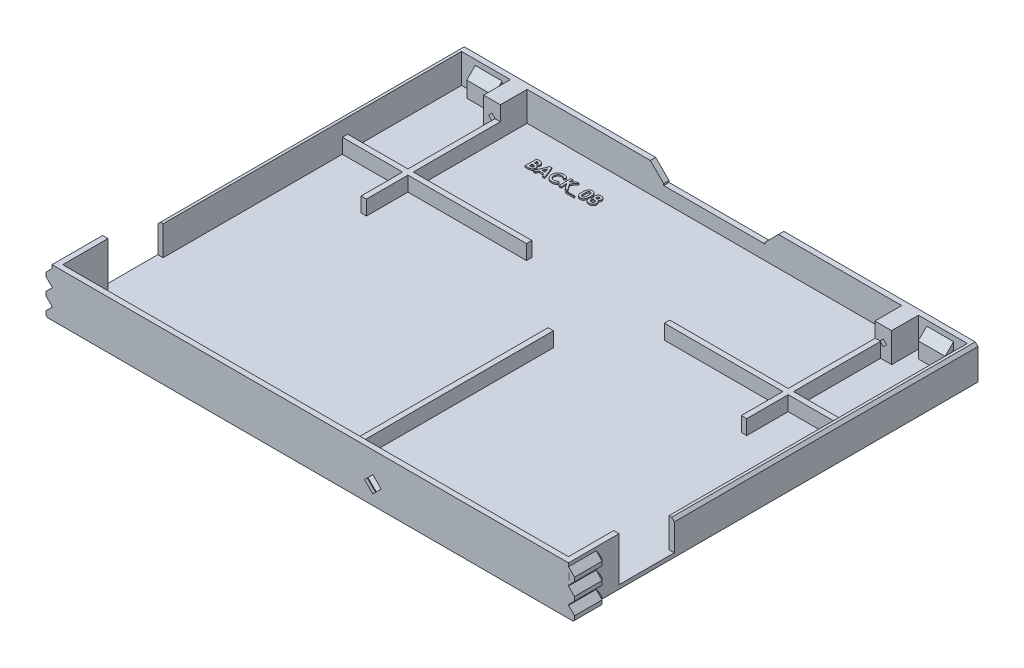
SolidWorks part; units mm, degrees
ref_plane "Front Plane" through (0, 0, 0) normal (0, 0, 1) x (1, 0, 0)
ref_plane "Top Plane" through (0, 0, 0) normal (0, 1, 0) x (1, 0, 0)
ref_plane "Right Plane" through (0, 0, 0) normal (1, 0, 0) x (0, 0, -1)
sketch "Sketch1" plane through (0, 0, 0) normal (0, 1, 0) x (1, 0, 0)
  line L3 (-77.15, -61.17) -> (77.15, -61.17)
  line L5 (-77.15, 61.17) -> (77.15, -61.17) construction
  line L6 (-77.15, -61.17) -> (77.15, 61.17) construction
  line L13 (-77.15, 61.17) -> (-77.15, -61.17)
  line L18 (77.15, 61.17) -> (-77.15, 61.17)
  line L20 (77.15, 61.17) -> (77.15, -61.17)
  point P0 (0, 0)
  point P6 (0, 0)
  dimension "D3" = 154.3
  dimension "D1" = 154.3
  dimension "D2" = 122.34
extrude "flat_on_wall" add sketch "Sketch1" along normal blind 1.2
sketch "Sketch3" plane through (0, 0, 0) normal (0, 1, 0) x (1, 0, 0)
  line L0 (-77.15, -29.57) -> (-77.15, 61.17)
  line L1 (-77.15, 61.17) -> (-77.15, -61.17) construction
  line L2 (-77.15, 61.17) -> (-45.55, 61.17)
  line L3 (77.15, 61.17) -> (-77.15, 61.17) construction
  line L6 (-75.55, 59.57) -> (-75.55, -29.57)
  line L7 (-75.55, -29.57) -> (-77.15, -29.57)
  line L8 (45.55, 61.17) -> (77.15, 61.17)
  line L9 (77.15, 61.17) -> (77.15, -29.57)
  line L10 (77.15, -61.17) -> (77.15, 61.17) construction
  line L11 (77.15, -29.57) -> (75.55, -29.57)
  line L12 (75.55, -29.57) -> (75.55, 59.57)
  line L15 (-77.15, -46.07) -> (-77.15, -61.17)
  line L16 (-77.15, -61.17) -> (77.15, -61.17)
  line L17 (77.15, -61.17) -> (77.15, -46.07)
  line L18 (77.15, -46.07) -> (75.55, -46.07)
  line L19 (75.55, -46.07) -> (75.55, -59.57)
  line L20 (75.55, -59.57) -> (-75.55, -59.57)
  line L21 (-75.55, -59.57) -> (-75.55, -46.07)
  line L22 (-75.55, -46.07) -> (-77.15, -46.07)
  line L23 (-75.55, 59.57) -> (-60.95, 59.57)
  line L24 (-60.95, 59.57) -> (-60.95, 51.57)
  line L25 (-60.95, 51.57) -> (-55.95, 51.57)
  line L26 (-55.95, 51.57) -> (-55.95, 59.57)
  line L27 (-55.95, 59.57) -> (-45.55, 59.57)
  line L28 (75.55, 59.57) -> (60.95, 59.57)
  line L29 (60.95, 59.57) -> (60.95, 51.57)
  line L30 (60.95, 51.57) -> (55.95, 51.57)
  line L31 (55.95, 51.57) -> (55.95, 59.57)
  line L32 (55.95, 59.57) -> (45.55, 59.57)
  line L34 (-45.55, 59.57) -> (45.55, 59.57)
  line L36 (-45.55, 61.17) -> (45.55, 61.17)
  point P25 (-76.35, -46.07)
  dimension "D2" = 1.6
  dimension "D3" = 30
  dimension "D4" = 16.5
  dimension "D5" = 5
  dimension "D6" = 1.6
  dimension "D7" = 30
  dimension "D8" = 16.5
  dimension "D9" = 1.6
  dimension "D10" = 13.5
  dimension "D11" = 1.6
  dimension "D12" = 1.6
  dimension "D13" = 13.5
  dimension "D14" = 14.6
  dimension "D15" = 5
  dimension "D16" = 8
  dimension "D17" = 8
  dimension "D18" = 8
  dimension "D19" = 8
  dimension "D20" = 1.6
  dimension "D21" = 14.6
  dimension "D22" = 1.6
  dimension "D23" = 1.6
extrude "walls" add sketch "Sketch3" along normal blind 10
sketch "Sketch5" plane through (0, 0, 0) normal (1, 0, 0) x (0, 0, -1)
  line L0 (-61.17, 10) -> (-61.17, 0) construction
  line L5 (-61.17, 0) -> (-51.97, 0)
  line L6 (-61.17, 0) -> (-61.17, 2)
  line L7 (-61.17, 2) -> (-51.97, 2)
  line L8 (-51.97, 0) -> (-51.97, 2)
  line L9 (-61.17, 0) -> (61.17, 0) construction
  line L10 (-61.17, 10) -> (-51.97, 10)
  line L11 (-61.17, 5) -> (-51.97, 5)
  line L12 (-61.17, 5) -> (-61.17, 7)
  line L13 (-61.17, 7) -> (-51.97, 7)
  line L14 (-51.97, 5) -> (-51.97, 7)
  line L15 (-61.17, 10) -> (-61.17, 12)
  line L16 (-61.17, 12) -> (-51.97, 12)
  line L17 (-51.97, 10) -> (-51.97, 12)
  line L18 (-61.17, 10) -> (-46.07, 10) construction
  dimension "D1" = 0
  dimension "D2" = 9.2
  dimension "D3" = 2
  dimension "D4" = 9.2
  dimension "D5" = 2
  dimension "D6" = 3
  dimension "D7" = 2
extrude "rails" add sketch "Sketch5" along normal blind 0.75 from surface starting at face at (77.15, 5.3, 18.91)
sketch "Sketch6" plane through (0, 0, 0) normal (1, 0, 0) x (0, 0, -1)
  line L0 (-61.17, 12) -> (-51.97, 12)
  line L1 (-61.17, 2) -> (-51.97, 2)
  line L2 (-61.17, 2) -> (-61.17, 0)
  line L3 (-61.17, 0) -> (-51.97, 0)
  line L4 (-51.97, 2) -> (-51.97, 0)
  line L5 (-61.17, 7) -> (-51.97, 7)
  line L6 (-61.17, 7) -> (-61.17, 5)
  line L7 (-61.17, 5) -> (-51.97, 5)
  line L8 (-51.97, 7) -> (-51.97, 5)
  line L9 (-61.17, 12) -> (-61.17, 10)
  line L10 (-61.17, 10) -> (-51.97, 10)
  line L11 (-51.97, 12) -> (-51.97, 10)
  dimension "D1" = 9.2
  dimension "D2" = 9.2
  dimension "D3" = 2
  dimension "D4" = 2
  dimension "D5" = 2
extrude "rails-left" add sketch "Sketch6" along normal blind 0.1 and the other way blind 1.8 from surface starting at face at (-77.15, 5.3, 18.91)
sketch "Sketch7" plane through (0, 0, 0) normal (0, 1, 0) x (1, 0, 0)
  line L0 (-47.15, 46.17) -> (-47.15, 39.9043) construction
  line L1 (-44.69, 46.17) -> (-44.69, 43.37)
  line L2 (-49.61, 46.17) -> (-49.61, 43.37)
  line L3 (77.15, 61.17) -> (-77.15, 61.17) construction
  line L4 (-77.15, -29.57) -> (-77.15, -46.07) construction
  line L5 (47.15, 46.17) -> (47.15, 39.9043) construction
  line L6 (49.61, 46.17) -> (49.61, 43.37)
  line L7 (44.69, 46.17) -> (44.69, 43.37)
  line L9 (77.15, -29.57) -> (77.15, 61.17) construction
  line L10 (77.15, 61.17) -> (-77.15, 61.17) construction
  line L13 (-77.05, -61.17) -> (77.15, -61.17) construction
  line L14 (-0.45, 8.83) -> (-0.45, 2.5643) construction
  line L15 (2.01, 8.83) -> (2.01, 6.03)
  line L16 (-2.91, 8.83) -> (-2.91, 6.03)
  line L17 (77.15, -46.07) -> (77.15, -29.57) construction
  arc A0 (-44.69, 46.17) -> (-49.61, 46.17) centre (-47.15, 46.17) ccw
  arc A3 (-44.69, 43.37) -> (-49.61, 43.37) centre (-47.15, 39.9043) cw
  arc A4 (49.61, 46.17) -> (44.69, 46.17) centre (47.15, 46.17) ccw
  arc A5 (49.61, 43.37) -> (44.69, 43.37) centre (47.15, 39.9043) cw
  arc A8 (2.01, 8.83) -> (-2.91, 8.83) centre (-0.45, 8.83) ccw
  arc A9 (2.01, 6.03) -> (-2.91, 6.03) centre (-0.45, 2.5643) cw
  point P2 (-47.9176, 44.8712)
  point P13 (43.1175, 41.9506)
  dimension "D1" = 15
  dimension "D5" = 2.46
  dimension "D9" = 4.25
  dimension "D2" = 30
  dimension "D3" = 15
  dimension "D4" = 30
  dimension "D6" = 6.2657
  dimension "D7" = 77.6
  dimension "D8" = 70
extrude "Cut-Extrude7" [suppressed] cut sketch "Sketch7" against normal through all from surface starting at face at (0, 1.2, -7.1)
sketch "Sketch8" plane through (0, 0, -51.57) normal (0, 0, 1) x (1, 0, 0)
  line L0 (-60.95, 10) -> (-60.95, 1.2) construction
  line L1 (-60.95, 10) -> (-55.95, 10) construction
  line L2 (55.95, 10) -> (55.95, 1.2) construction
  line L3 (55.95, 10) -> (60.95, 10) construction
  line L4 (-75.55, 10) -> (-60.95, 10) construction
  line L5 (-63.45, 3) -> (-71.45, 3)
  line L6 (-63.45, 3) -> (-63.45, 8)
  line L7 (-63.45, 8) -> (-71.45, 8)
  line L8 (-71.45, 3) -> (-71.45, 8)
  line L9 (-60.95, 1.2) -> (-75.55, 1.2) construction
  line L10 (-75.55, 10) -> (-75.55, 1.2) construction
  line L11 (-75.55, 10) -> (-75.55, 1.2)
  line L12 (-75.55, 1.2) -> (0, 1.2)
  line L13 (0, 1.2) -> (0, 10)
  line L14 (71.45, 3) -> (71.45, 8)
  line L15 (63.45, 8) -> (71.45, 8)
  line L16 (63.45, 3) -> (63.45, 8)
  line L17 (63.45, 3) -> (71.45, 3)
  line L18 (-58.45, 6.6) -> (-59.45, 5.6)
  line L19 (-59.45, 5.6) -> (-58.45, 4.6)
  line L20 (-58.45, 4.6) -> (-57.45, 5.6)
  line L21 (-57.45, 5.6) -> (-58.45, 6.6)
  line L22 (58.45, 6.6) -> (59.45, 5.6)
  line L23 (59.45, 5.6) -> (58.45, 4.6)
  line L24 (58.45, 4.6) -> (57.45, 5.6)
  line L25 (57.45, 5.6) -> (58.45, 6.6)
  circle A0 centre (-58.45, 5.6) radius 1 construction
  circle A1 centre (58.45, 5.6) radius 1 construction
  circle A2 centre (58.45, 5.6) radius 1 construction
  dimension "D1" = 2.5
  dimension "D3" = 2.5
  dimension "D2" = 4.4
  dimension "D4" = 4.4
  dimension "D5" = 5
  dimension "D6" = 8
  dimension "D7" = 5
  dimension "D8" = 2
  dimension "D9" = 1.8
  dimension "D10" = 75.55
extrude "Cut-Extrude8" cut sketch "Sketch8" against normal blind 10 contours A0 | A1 | L8 L5 L6 L7 | L16 L17 L14 L15 | L18 L19 L20 L21 | L24 L25 L22 L23 region at (-67.45, 5.5, -51.57) region at (67.45, 5.5, -51.57)
sketch "Sketch9" plane through (0, 1.2, 0) normal (0, 1, 0) x (1, 0, 0)
  line L0 (-75.55, 59.57) -> (-75.55, -29.57) construction
  line L7 (0.05, -59.57) -> (0.05, 37.2031)
  line L8 (-75.55, -59.57) -> (75.55, -59.57) construction
  line L9 (75.55, -59.57) -> (75.55, -46.07) construction
  line L12 (-55.95, 51.57) -> (-57.55, 51.57)
  line L13 (-55.95, 51.57) -> (-55.95, 25.5612)
  line L14 (-55.95, 11.57) -> (-57.55, 11.57)
  line L15 (-57.55, 51.57) -> (-57.55, 25.5612)
  line L16 (-75.55, 25.5612) -> (-57.55, 25.5612)
  line L17 (-75.55, 25.5612) -> (-75.55, 23.9612)
  line L18 (-75.55, 23.9612) -> (-57.55, 23.9612)
  line L19 (-20.55, 25.5612) -> (-20.55, 23.9612)
  line L20 (-55.95, 25.5612) -> (-20.55, 25.5612)
  line L21 (-55.95, 23.9612) -> (-20.55, 23.9612)
  line L22 (-55.95, 23.9612) -> (-55.95, 11.57)
  line L23 (-57.55, 23.9612) -> (-57.55, 11.57)
  line L24 (57.65, 23.9612) -> (57.65, 11.57)
  line L25 (56.05, 23.9612) -> (56.05, 11.57)
  line L26 (56.05, 23.9612) -> (20.65, 23.9612)
  line L27 (56.05, 25.5612) -> (20.65, 25.5612)
  line L28 (20.65, 25.5612) -> (20.65, 23.9612)
  line L29 (75.65, 23.9612) -> (57.65, 23.9612)
  line L30 (75.65, 25.5612) -> (75.65, 23.9612)
  line L31 (75.65, 25.5612) -> (57.65, 25.5612)
  line L32 (57.65, 51.57) -> (57.65, 25.5612)
  line L33 (56.05, 11.57) -> (57.65, 11.57)
  line L34 (56.05, 51.57) -> (56.05, 25.5612)
  line L35 (56.05, 51.57) -> (57.65, 51.57)
  line L36 (-75.55, -59.57) -> (75.55, -59.57) construction
  line L37 (4.45, -59.57) -> (6.05, -59.57)
  line L38 (4.45, -59.57) -> (4.45, 5.43)
  line L39 (4.45, 5.43) -> (6.05, 5.43)
  line L40 (6.05, -59.57) -> (6.05, 5.43)
  line L41 (-75.55, 59.57) -> (-75.55, -29.57) construction
  line L42 (-55.95, 51.57) -> (-60.95, 51.57) construction
  point P39 (5.25, 5.43)
  point P42 (-56.75, 11.57)
  line M17 (-75.55, -59.57) -> (75.55, -59.57)
  line M22 (75.55, -29.57) -> (75.55, 59.57)
  line M25 (60.95, 51.57) -> (55.95, 51.57)
  line M29 (-55.95, 51.57) -> (-60.95, 51.57)
  line M32 (-75.55, 59.57) -> (-75.55, -29.57)
  dimension "D1" = 1.6
  dimension "D2" = 6
  dimension "D3" = 75.5
  dimension "D4" = 1.6
  dimension "D5" = 1.6
  dimension "D6" = 65
  dimension "D7" = 55
  dimension "D8" = 40
extrude "Boss-Extrude8" add sketch "Sketch9" along normal blind 4.4 contours L18 L23 L14 L22 L21 L19 L20 L13 L15 L16 M29 M32 | L40 L39 L38 M17 | L34 L27 L28 L26 L25 L33 L24 L29 L31 L32 M25 M22 region at (-56.6301, 1.2, -38.5656) region at (56.9707, 1.2, -17.7656) region at (5.25, 1.2, 27.07)
sketch "Sketch16" plane through (0, 10, 0) normal (0, 1, 0) x (1, 0, 0)
  line L2 (77.15, -61.17) -> (77.15, -46.07)
  line L3 (77.15, -46.07) -> (75.55, -46.07)
  line L4 (75.55, -46.07) -> (75.55, -59.57)
  line L5 (75.55, -59.57) -> (-75.55, -59.57)
  line L6 (-75.55, -59.57) -> (-75.55, -46.07)
  line L7 (-75.55, -46.07) -> (-77.15, -46.07)
  line L8 (-77.15, -46.07) -> (-77.15, -61.17)
  line L11 (-77.15, -61.17) -> (77.15, -61.17)
extrude "Boss-Extrude9" add sketch "Sketch16" along normal blind 4.4
chamfer "Rail Chamfers" distance 0.8 angle 45 10 edges at (77.525, 7, 51.97) (77.525, 5, 51.97) (77.525, 2, 51.97) (77.525, 0, 51.97) (-78.05, 12, 51.97) (-78.05, 10, 51.97) (-78.05, 7, 51.97) (-78.05, 5, 51.97) (-78.05, 2, 51.97) (-78.05, 0, 51.97)
chamfer "Rail Chamfers 2" distance 0.8 angle 45 2 edges at (77.525, 12, 51.97) (77.525, 10, 51.97)
chamfer "Wall Chamfers" distance 0.8 angle 45 2 edges at (77.15, 10, -15.8) (-77.15, 10, -15.8)
sketch "Sketch18" plane through (0, 0, -61.17) normal (0, 0, -1) x (-1, 0, 0)
  line L0 (-76.35, 10) -> (76.35, 10) construction
  line L1 (-15.15, 10) -> (15.15, 10)
  line L2 (-15.15, 10) -> (-15.15, 5.5)
  line L3 (-15.15, 5.5) -> (15.15, 5.5)
  line L4 (15.15, 10) -> (15.15, 5.5)
  line L5 (-77.15, 9.2) -> (-77.15, 0) construction
  line L6 (77.15, 9.2) -> (77.15, 0) construction
  dimension "D1" = 62
  dimension "D2" = 62
  dimension "D3" = 4.5
extrude "Ribbon Hole" cut sketch "Sketch18" against normal blind 10
chamfer "Chamfer1" distance 0.4 angle 45 30 edges at (-78.95, 10.4, 52.37) (-78.95, 11, 51.97) (-78.95, 11.6, 52.37) (-78.95, 12, 56.97) (-78.95, 11, 61.17) (-78.95, 10, 56.97) (-78.95, 5.4, 52.37) (-78.95, 6, 51.97) (-78.95, 6.6, 52.37) (-78.95, 7, 56.97) (-78.95, 6, 61.17) (-78.95, 5, 56.97) (-78.95, 0.4, 52.37) (-78.95, 1, 51.97) (-78.95, 1.6, 52.37) (-78.95, 2, 56.97) (-78.95, 1, 61.17) (-78.95, 0, 56.97) (77.9, 1.6, 52.37) (77.9, 1, 51.97) (77.9, 0.4, 52.37) (77.9, 0, 56.97) (77.9, 2, 56.97) (77.9, 1, 61.17) (77.9, 6, 61.17) (77.9, 5, 56.97) (77.9, 5.4, 52.37) (77.9, 6, 51.97) (77.9, 6.6, 52.37) (77.9, 7, 56.97)
chamfer "Chamfer2" distance 0.4 angle 45 6 edges at (77.9, 11, 51.97) (77.9, 10.4, 52.37) (77.9, 10, 56.97) (77.9, 11, 61.17) (77.9, 11.6, 52.37) (77.9, 12, 56.97)
sketch "Sketch19" plane through (0, 0, 61.17) normal (0, 0, 1) x (1, 0, 0)
  line L0 (-78.55, 0) -> (77.5, 0) construction
  line L2 (16.2, 5.5) -> (16.2, 14.5133) construction
  line L3 (21.2, 5.5) -> (21.2, 14.5133) construction
  line L4 (16.2, 14.5133) -> (21.2, 14.5133) construction
  line L6 (18.7, 3) -> (16.2, 5.5)
  line L7 (18.7, 3) -> (21.2, 5.5)
  line L8 (21.2, 5.5) -> (18.7, 8)
  line L9 (18.7, 8) -> (16.2, 5.5)
  arc A0 (16.2, 5.5) -> (21.2, 5.5) centre (18.7, 5.5) ccw construction
  dimension "D1" = 5.5
  dimension "D3" = 5
  dimension "D2" = 18.7
extrude "Cut-Extrude9" cut sketch "Sketch19" against normal blind 10
sketch "Sketch20" plane through (0, 0, 61.17) normal (0, 0, 1) x (1, 0, 0)
  line L0 (-78.95, 11.6) -> (-78.95, 10.4)
  line L1 (-78.95, 10.4) -> (-77.05, 8.5)
  line L2 (-78.95, 11.6) -> (-77.15, 13.4)
  line L4 (-77.15, 14.4) -> (-77.15, 12) construction
  line L7 (-78.95, 1.6) -> (-77.05, 3.5)
  line L9 (-78.95, 5.4) -> (-77.05, 3.5)
  line L10 (-78.95, 6.6) -> (-78.95, 5.4)
  line L11 (-78.95, 6.6) -> (-77.05, 8.5)
  line L12 (-78.95, 1.6) -> (-78.95, 0.4)
  line L13 (-78.95, 0.4) -> (-78.55, 0)
  line L15 (-78.55, 10) -> (-78.95, 10.4) construction
  line L16 (-77.15, 13.4) -> (-76.932, 13.4)
  line L19 (-78.55, 0) -> (-76.932, 0)
  line L22 (-78.55, 7) -> (-78.95, 6.6) construction
  line L23 (-76.932, 13.4) -> (-76.932, 0)
extrude "Boss-Extrude11" add sketch "Sketch20" against normal blind 9.25
sketch "Sketch21" plane through (-71.45, 0, 0) normal (1, 0, 0) x (0, 0, -1)
  line L0 (61.17, 8) -> (58.4281, 5.2665)
  line L1 (58.4281, 5.2665) -> (58.4281, 1.2)
  line L2 (59.57, 1.2) -> (25.5612, 1.2) construction
  line L3 (57.0393, 1.2) -> (57.0393, 5.8819)
  line L4 (57.0393, 5.8819) -> (61.17, 10)
  line L6 (58.4281, 1.2) -> (57.0393, 1.2)
  line L7 (61.17, 10) -> (61.17, 8)
extrude "Boss-Extrude17" add sketch "Sketch21" along normal blind 8
mirror "Mirror2" about plane through (0, 0, 0) normal (1, 0, 0) of "Boss-Extrude17", "Boss-Extrude11"
chamfer "Chamfer3" distance 1 angle 45 18 edges at (-78.75, 0.2, 51.92) (-78.95, 1, 51.92) (-78.05, 2.5, 51.92) (-78.05, 4.5, 51.92) (-78.95, 6, 51.92) (-78.05, 7.5, 51.92) (-78.05, 9.5, 51.92) (-78.95, 11, 51.92) (-78.05, 12.5, 51.92) (78.75, 0.2, 51.92) (78.95, 1, 51.92) (78.05, 2.5, 51.92) (78.05, 4.5, 51.92) (78.95, 6, 51.92) (78.05, 7.5, 51.92) (78.05, 9.5, 51.92) (78.95, 11, 51.92) (78.05, 12.5, 51.92)
chamfer "Chamfer4" distance 4 angle 45 2 edges at (15.15, 10, -60.37) (-15.15, 10, -60.37)
sketch "Sketch22" plane through (0, 1.2, 0) normal (0, 1, 0) x (1, 0, 0)
  text T0 "<b>BACK_08</b>"
extrude "Boss-Extrude18" add sketch "Sketch22" along normal blind 0.4
chamfer "Chamfer5" distance 0.8 angle 45 4 edges at (19.95, 6.75, 59.57) (19.95, 4.25, 59.57) (17.45, 4.25, 59.57) (17.45, 6.75, 59.57)
